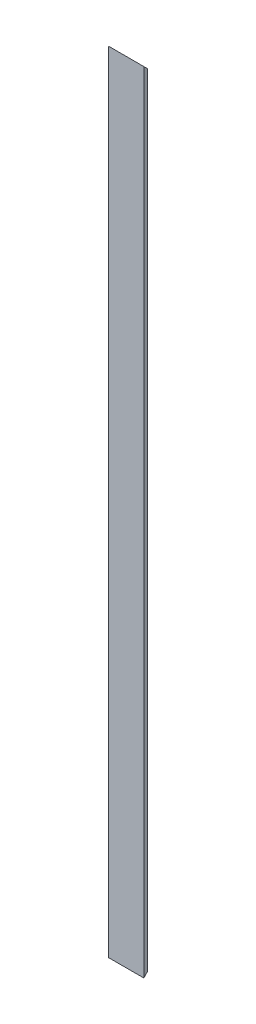
SolidWorks part; units mm, degrees
ref_plane "Спереди" through (0, 0, 0) normal (0, 0, 1) x (1, 0, 0)
ref_plane "Сверху" through (0, 0, 0) normal (0, 1, 0) x (1, 0, 0)
ref_plane "Справа" through (0, 0, 0) normal (1, 0, 0) x (0, 0, -1)
sketch "Эскиз1" plane through (0, 0, 0) normal (0, 1, 0) x (1, 0, 0)
  line L0 (0, 45) -> (0, 0)
  line L1 (0, 0) -> (45, 0)
extrude "Вытянуть-Тонкостенный1" add sketch "Эскиз1" along normal blind 1000 thin thin type one direction reverse wall 5
sketch "Эскиз2" plane through (0, 0, 0) normal (-1, 0, 0) x (0, 0, 1)
  line L0 (0, 0) -> (-45, 45)
  line L1 (-45, 1000) -> (-45, 0) construction
  line L2 (-45, 0) -> (-45, 45)
  line L3 (-45, 0) -> (0, 0)
  line L4 (-45, 500) -> (36.3553, 500) construction
  line L5 (-45, 1000) -> (0, 1000)
  line L6 (-45, 1000) -> (-45, 955)
  line L7 (0, 1000) -> (-45, 955)
extrude "Вырез-Вытянуть1" cut sketch "Эскиз2" against normal through all
